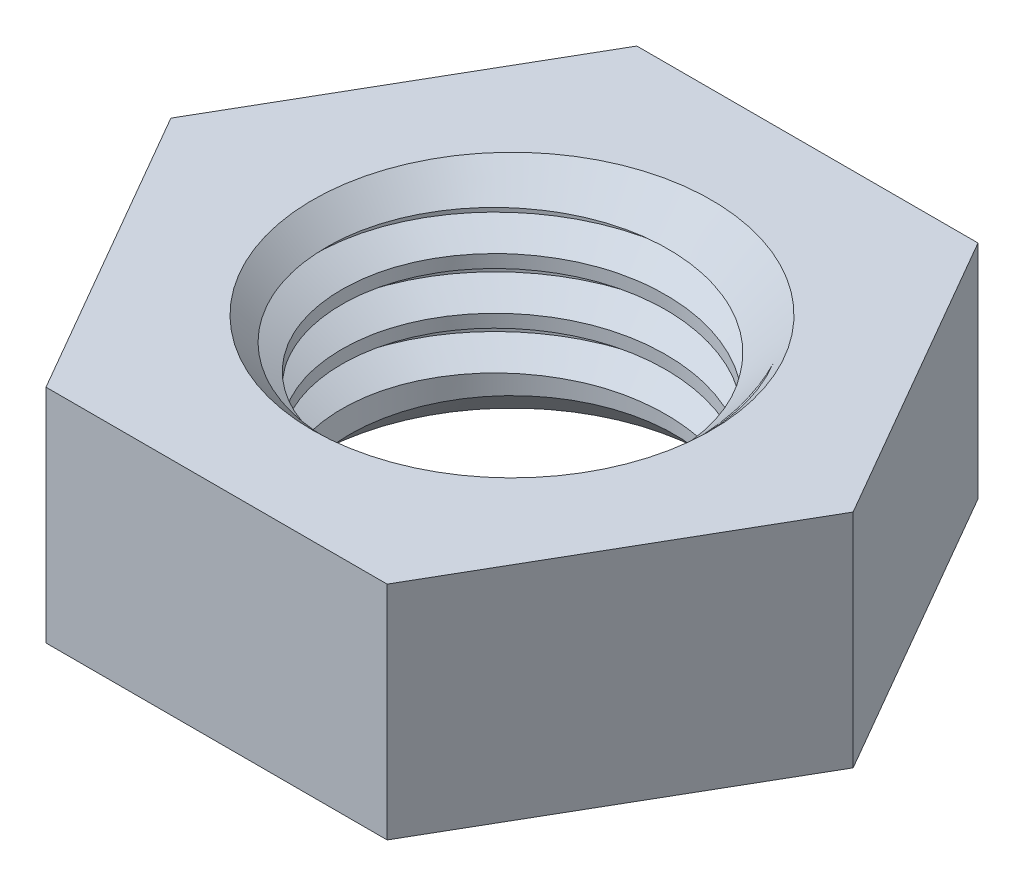
SolidWorks part; units mm, degrees
ref_plane "Front Plane" through (0, 0, 0) normal (0, 0, 1) x (1, 0, 0)
ref_plane "Top Plane" through (0, 0, 0) normal (0, 1, 0) x (1, 0, 0)
ref_plane "Right Plane" through (0, 0, 0) normal (1, 0, 0) x (0, 0, -1)
sketch "Sketch2" plane through (0, 0, 0) normal (0, 1, 0) x (1, 0, 0)
  line L1 (4.6188, 0) -> (2.3094, 4)
  line L2 (2.3094, 4) -> (-2.3094, 4)
  line L3 (-2.3094, 4) -> (-4.6188, 0)
  line L4 (-4.6188, 0) -> (-2.3094, -4)
  line L5 (-2.3094, -4) -> (2.3094, -4)
  line L6 (2.3094, -4) -> (4.6188, 0)
  circle A0 centre (0, 0) radius 4 construction
  circle A1 centre (0, 0) radius 2.2
  dimension "D1" = 8
extrude "Boss-Extrude1" add sketch "Sketch2" along normal blind 3
chamfer "Chamfer1" distance 0.5 angle 45 2 edges at (0, 0, 2.2) (0, 3, 2.2)
thread "Thread1" pitch 0.7 method cut profile "Thread Profile1" start angle 0, offset 0, length 4, pitch 0.7, diameter 4.4
ref_plane "Plane1" through (2.2, 0.5, 0) normal (0, 0, 1) x (1, 0, 0)
sketch "Thread Profile1" plane through (2.2, 0.5, 0) normal (0, 0, 1) x (1, 0, 0)
  line L0 (0, 0) -> (0, 0.7) construction
  line L1 (0, 0) -> (0.3789, 0.2187)
  line L2 (0.3789, 0.2187) -> (0.3789, 0.3062)
  line L3 (0.3789, 0.3062) -> (0, 0.525)
  line L4 (0.3789, 0.2625) -> (0, 0.2625) construction
  line L11 (0, 0) -> (0, 0.525)
  point P2 (0, 0)
  dimension "Pitch" = 0.7
  dimension "Profile_Angle" = 60
  dimension "Profile_Land" = 0.0875
  dimension "Profile_Height" = 0.3789
